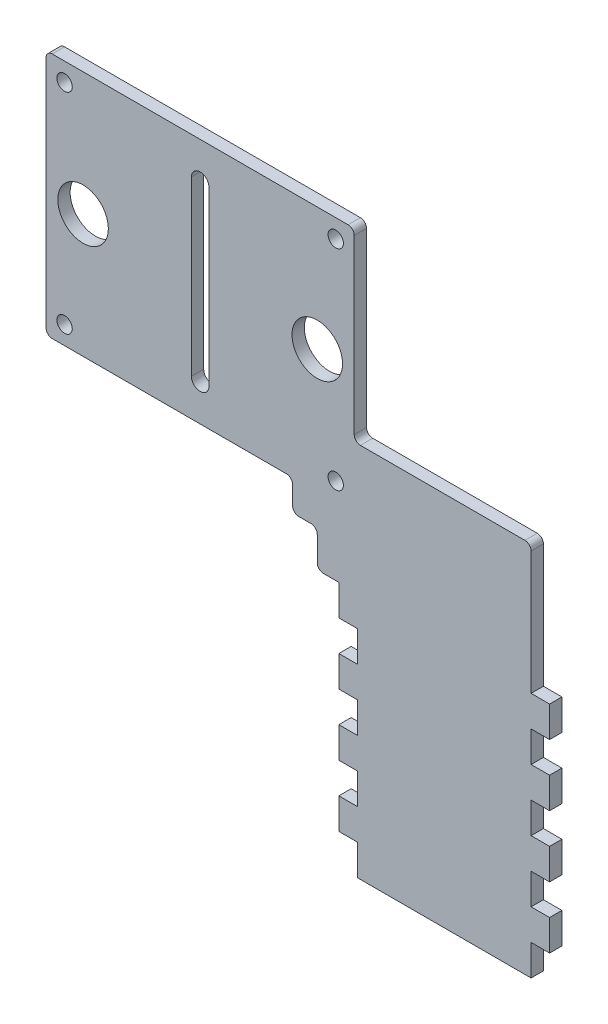
SolidWorks part; units mm, degrees
ref_plane "Front Plane" through (0, 0, 0) normal (0, 0, 1) x (1, 0, 0)
ref_plane "Top Plane" through (0, 0, 0) normal (0, 1, 0) x (1, 0, 0)
ref_plane "Right Plane" through (0, 0, 0) normal (1, 0, 0) x (0, 0, -1)
sketch "Sketch1" plane through (0, 0, 0) normal (0, 0, 1) x (1, 0, 0)
  line L1 (0, 0) -> (50, 0)
  line L2 (0, 0) -> (0, 40)
  line L3 (0, 40) -> (50, 40)
  line L4 (50, 0) -> (50, 40)
  line L5 (50, 0) -> (78.7, 0)
  line L6 (50, 0) -> (50, -51)
  line L7 (50, -51) -> (78.7, -51)
  line L8 (78.7, 0) -> (78.7, -51)
  line L9 (50, 0) -> (78.7, 0)
  line L12 (78.7, 0) -> (78.7, -21)
  line L13 (78.7, 0) -> (50, 0)
  line L14 (78.7, 0) -> (78.7, 10)
  line L15 (78.7, 10) -> (50, 10)
  line L16 (50, 0) -> (50, 10)
  line L17 (40, 0) -> (50, 0)
  line L18 (40, 0) -> (40, -5)
  line L19 (40, -5) -> (50, -5)
  line L20 (50, 0) -> (50, -5)
  line L21 (50, -5) -> (44, -5)
  line L22 (50, -5) -> (50, -11)
  line L23 (50, -11) -> (44, -11)
  line L24 (44, -5) -> (44, -11)
  dimension "D1" = 50
  dimension "D2" = 40
  dimension "D3" = 28.7
  dimension "D4" = 51
  dimension "D5" = 0
  dimension "D6" = 10
  dimension "D7" = 0
  dimension "D8" = 0
  dimension "D9" = 0
  dimension "D10" = 10
  dimension "D11" = 5
  dimension "D12" = 0
  dimension "D13" = 0
  dimension "D14" = 6
  dimension "D15" = 6
extrude "plate_body" add sketch "Sketch1" along normal blind 2 contours L1 L4 L3 L2 | L8 L5 L1 L6 L7 | L14 L15 L4 L5 | L18 L19 L6 L1 | L19 L24 L23 L6 region at (25, 20, 0) region at (45, -2.5, 0) region at (64.35, 5, 0) region at (64.35, -25.5, 0) region at (47, -8, 0)
sketch "Sketch2" plane through (0, 0, 2) normal (0, 0, 1) x (1, 0, 0)
  line L2 (0, 0) -> (0, 40) construction
  line L3 (0, 40) -> (50, 40) construction
  circle A0 centre (6, 20) radius 4.1
  circle A1 centre (44, 20) radius 4.1
  dimension "D1" = 38
  dimension "D2" = 8.2
  dimension "D3" = 8.2
  dimension "D4" = 6
  dimension "D5" = 20
  dimension "D6" = 20
extrude "shaft_bearings" cut sketch "Sketch2" against normal through all
sketch "Sketch4" plane through (0, 0, 2) normal (0, 0, 1) x (1, 0, 0)
  line L0 (25, 34) -> (25, 6) construction
  line L1 (26.425, 34) -> (26.425, 6)
  line L2 (23.575, 34) -> (23.575, 6)
  line L3 (0, 0) -> (40, 0) construction
  line L5 (0, 0) -> (0, 40) construction
  arc A0 (26.425, 34) -> (23.575, 34) centre (25, 34) ccw
  arc A1 (23.575, 6) -> (26.425, 6) centre (25, 6) ccw
  point P2 (25, 20)
  dimension "D4" = 6
  dimension "D1" = 2.85
  dimension "D2" = 28
  dimension "D3" = 25
extrude "slot" cut sketch "Sketch4" against normal through all
sketch "Sketch5" plane through (0, 0, 2) normal (0, 0, 1) x (1, 0, 0)
  line L0 (0, 40) -> (50, 40) construction
  line L1 (0, 0) -> (0, 40) construction
  line L3 (50, 10) -> (50, 40) construction
  line L4 (0, 0) -> (40, 0) construction
  circle A0 centre (3, 37) radius 1.25
  circle A1 centre (47, 37) radius 1.25
  circle A2 centre (3, 3) radius 1.25
  circle A3 centre (47, 3) radius 1.25
  dimension "D1" = 2.5
  dimension "D2" = 2.5
  dimension "D3" = 2.5
  dimension "D4" = 2.5
  dimension "D5" = 3
  dimension "D6" = 3
  dimension "D7" = 3
  dimension "D8" = 3
  dimension "D9" = 3
  dimension "D10" = 3
  dimension "D11" = 3
  dimension "D12" = 3
extrude "bolt_holes" cut sketch "Sketch5" against normal through all
sketch "Sketch6" plane through (0, 0, 2) normal (0, 0, 1) x (1, 0, 0)
  line L0 (50, -51) -> (78.7, -51) construction
  line L1 (50, -11) -> (50.5, -11)
  line L2 (50, -11) -> (50, -51)
  line L3 (50, -51) -> (50.5, -51)
  line L4 (50.5, -11) -> (50.5, -51)
  line L5 (50, -11) -> (44, -11) construction
  dimension "D1" = 0.5
  dimension "D2" = 0
extrude "Cut-Extrude1" cut sketch "Sketch6" against normal through all
sketch "Sketch8" plane through (0, 0, 2) normal (0, 0, 1) x (1, 0, 0)
  line L0 (50.5, -36) -> (47.5, -36)
  line L1 (50.5, -46) -> (47.5, -46)
  line L2 (50.5, -46) -> (50.5, -41)
  line L3 (50.5, -41) -> (47.5, -41)
  line L4 (47.5, -46) -> (47.5, -41)
  line L5 (78.7, -46) -> (81.7, -46)
  line L6 (78.7, -46) -> (78.7, -41)
  line L7 (78.7, -41) -> (81.7, -41)
  line L8 (81.7, -46) -> (81.7, -41)
  line L9 (50.5, -36) -> (50.5, -31)
  line L10 (50.5, -31) -> (47.5, -31)
  line L11 (47.5, -36) -> (47.5, -31)
  line L12 (78.7, -36) -> (81.7, -36)
  line L13 (78.7, -36) -> (78.7, -31)
  line L14 (78.7, -31) -> (81.7, -31)
  line L15 (81.7, -36) -> (81.7, -31)
  line L16 (50.5, -51) -> (50.5, -11) construction
  line L17 (78.7, -51) -> (78.7, 10) construction
  line L18 (50.5, -16) -> (47.5, -16)
  line L19 (50.5, -26) -> (47.5, -26)
  line L20 (50.5, -26) -> (50.5, -21)
  line L21 (50.5, -21) -> (47.5, -21)
  line L22 (47.5, -26) -> (47.5, -21)
  line L23 (78.7, -26) -> (81.7, -26)
  line L24 (78.7, -26) -> (78.7, -21)
  line L25 (78.7, -21) -> (81.7, -21)
  line L26 (81.7, -26) -> (81.7, -21)
  line L27 (50.5, -16) -> (50.5, -11)
  line L28 (50.5, -11) -> (47.5, -11)
  line L29 (47.5, -16) -> (47.5, -11)
  line L30 (78.7, -16) -> (81.7, -16)
  line L31 (78.7, -16) -> (78.7, -11)
  line L32 (78.7, -11) -> (81.7, -11)
  line L33 (81.7, -16) -> (81.7, -11)
  line L34 (50.5, -51) -> (78.7, -51) construction
  point P38 (80.2, -31)
  point P41 (80.2, -41)
  dimension "D1" = 5
  dimension "D2" = 5
  dimension "D3" = 3
  dimension "D4" = 3
  dimension "D5" = 5
  dimension "D6" = 5
  dimension "D7" = 3
  dimension "D8" = 3
  dimension "D9" = 0
  dimension "D10" = 0
  dimension "D11" = 5
  dimension "D12" = 5
  dimension "D13" = 5
  dimension "D14" = 5
  dimension "D15" = 3
  dimension "D16" = 3
  dimension "D17" = 5
  dimension "D18" = 5
  dimension "D19" = 3
  dimension "D20" = 3
  dimension "D21" = 5
  dimension "D22" = 5
  dimension "D25" = 0
  dimension "D26" = 0
  dimension "D27" = 5
  dimension "D28" = 5
  dimension "D29" = 10
  dimension "D30" = 10
extrude "finger_joints" add sketch "Sketch8" along direction (0, 0, 1) on the side against the normal up to surface (2 mm away) up to face at (48.25, 37, 0)
sketch "Sketch9" plane through (0, 0, 2) normal (0, 0, 1) x (1, 0, 0)
  line L0 (50.5, -51) -> (78.7, -51) construction
  line L1 (55.5, -23) -> (63.5, -23)
  line L2 (55.5, -23) -> (55.5, -39)
  line L3 (55.5, -39) -> (63.5, -39)
  line L4 (63.5, -23) -> (63.5, -39)
  line L5 (50.5, -51) -> (50.5, -46) construction
  dimension "D1" = 8
  dimension "D2" = 16
  dimension "D3" = 12
  dimension "D4" = 5
extrude "Cut-Extrude2" [suppressed] cut sketch "Sketch9" against normal through all
fillet "1mm_fillets" radius 1 9 edges at (44, -11, 1) (44, -5, 1) (40, -5, 1) (40, 0, 1) (78.7, 10, 1) (50, 10, 1) (50, 40, 1) (0, 0, 1) (0, 40, 1)
